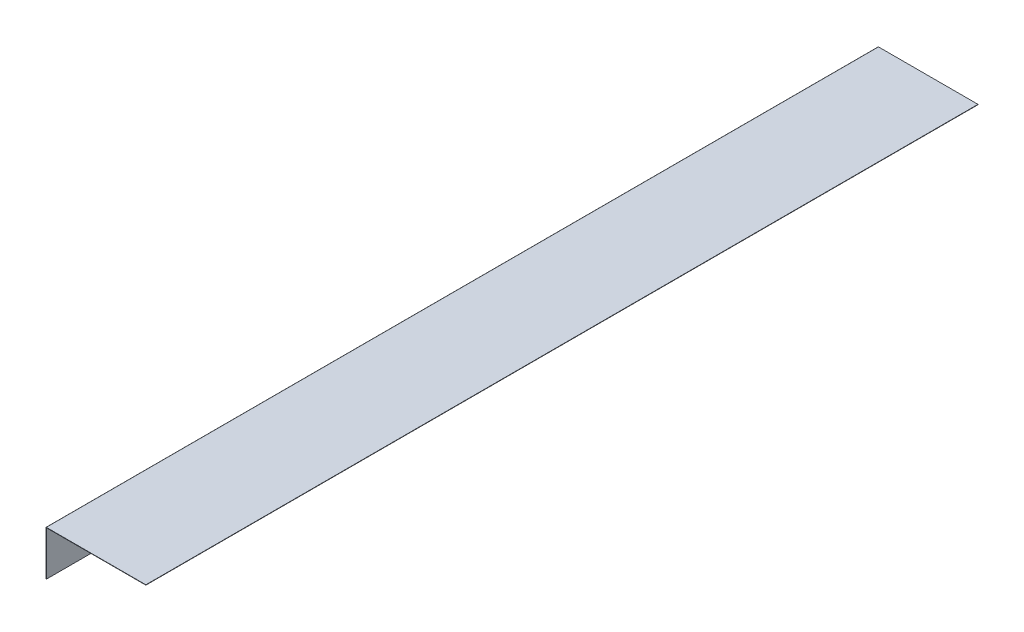
SolidWorks part; units mm, degrees
ref_plane "Front Plane" through (0, 0, 0) normal (0, 0, 1) x (1, 0, 0)
ref_plane "Top Plane" through (0, 0, 0) normal (0, 1, 0) x (1, 0, 0)
ref_plane "Right Plane" through (0, 0, 0) normal (1, 0, 0) x (0, 0, -1)
sketch "Sketch1" plane through (0, 0, 0) normal (0, 0, 1) x (1, 0, 0)
  line L0 (0, 0) -> (0, 135)
  line L1 (0, 135) -> (300, 135)
  line L2 (300, 135) -> (300, 134)
  line L3 (300, 134) -> (1, 134)
  line L4 (1, 134) -> (1, 0)
  line L5 (1, 0) -> (0, 0)
  point P6 (0.8944, 0.4473)
  point P8 (0.9983, 0.0581)
  dimension "D1" = 1
  dimension "D2" = 1
  dimension "D3" = 300
  dimension "D4" = 135
extrude "Boss-Extrude1" add sketch "Sketch1" along normal blind 2500
fillet "Fillet1" radius 1 2 edges at (0, 135, 1250) (1, 134, 1250)
